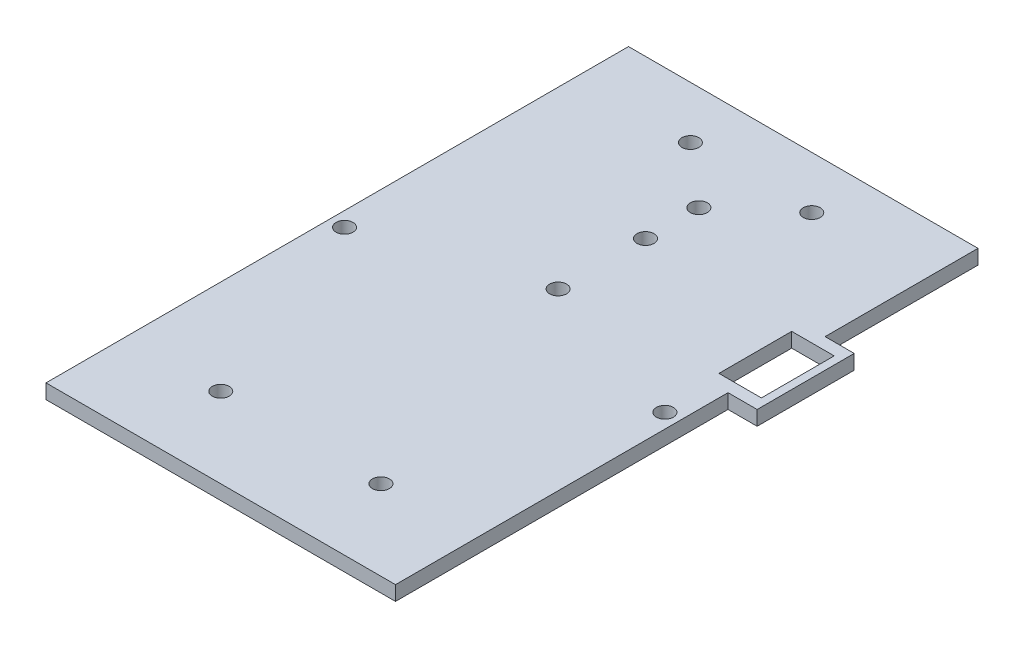
SolidWorks part; units mm, degrees
ref_plane "Front Plane" through (0, 0, 0) normal (0, 0, 1) x (1, 0, 0)
ref_plane "Top Plane" through (0, 0, 0) normal (0, 1, 0) x (1, 0, 0)
ref_plane "Right Plane" through (0, 0, 0) normal (1, 0, 0) x (0, 0, -1)
sketch "Sketch1" plane through (0, 0, 0) normal (0, 1, 0) x (1, 0, 0)
  line L0 (0, 0) -> (0, 50000) construction
  line L1 (36, -60) -> (-36, -60)
  line L2 (36, -60) -> (36, 60)
  line L3 (36, 60) -> (-36, 60)
  line L4 (-36, -60) -> (-36, 60)
  line L5 (36, -60) -> (-36, 60) construction
  line L6 (36, 60) -> (-36, -60) construction
  line L7 (0, 18.5) -> (36, 18.5) construction
  line L8 (0, 9.5) -> (0, -1.5)
  line L9 (0, 0) -> (50000, 0) construction
  line L10 (-20.7309, 49.25) -> (20.7309, 49.25) construction
  line L11 (30, 8.5) -> (42, 8.5)
  line L12 (30, 8.5) -> (30, 28.5)
  line L13 (30, 28.5) -> (42, 28.5)
  line L14 (42, 8.5) -> (42, 28.5)
  line L15 (30, 8.5) -> (42, 28.5) construction
  line L16 (30, 28.5) -> (42, 8.5) construction
  line L17 (40.375, 11) -> (31.625, 11)
  line L18 (40.375, 11) -> (40.375, 26)
  line L19 (40.375, 26) -> (31.625, 26)
  line L20 (31.625, 11) -> (31.625, 26)
  line L21 (40.375, 11) -> (31.625, 26) construction
  line L22 (40.375, 26) -> (31.625, 11) construction
  circle A0 centre (-33, -1.5) radius 1.75
  circle A1 centre (33, -1.5) radius 1.75
  circle A2 centre (-16.5, -43.5) radius 1.75
  circle A3 centre (16.5, -43.5) radius 1.75
  circle A4 centre (0, 27.5) radius 1.75
  circle A5 centre (0, 9.5) radius 1.75
  circle A10 centre (0, 38.5) radius 1.75
  circle A11 centre (0, 38.5) radius 1.75 construction
  circle A12 centre (-12.5, 49.25) radius 1.75
  circle A13 centre (12.5, 49.25) radius 1.75
  point P0 (0, 0)
  point P29 (36, 0)
  point P32 (36, 18.5)
  point P44 (0, 60)
  point P45 (0, 38.5)
  point P46 (0, 49.25)
  point P47 (0, 46.9563)
  point P48 (0, 38.5)
  point P49 (0, 0)
  point P52 (0, 49.25)
  point P53 (0, 0)
  point P54 (0, 0)
  point P55 (0, 0)
  dimension "D3" = 3.5
  dimension "D4" = 3.5
  dimension "D5" = 33
  dimension "D6" = 3.5
  dimension "D7" = 3.5
  dimension "D10" = 3.5
  dimension "D11" = 3.5
  dimension "D15" = 20
  dimension "D16" = 12
  dimension "D17" = 15
  dimension "D19" = 66
  dimension "D12" = 9
  dimension "D20" = 3.5
  dimension "D21" = 3.5
  dimension "D1" = 120
  dimension "D2" = 72
  dimension "D8" = 42
  dimension "D9" = 16.5
  dimension "D13" = 18
  dimension "D14" = 11
  dimension "D18" = 8.75
  dimension "D22" = 25
extrude "Boss-Extrude1" add sketch "Sketch1" along normal blind 3 contours L12 L13 L2 L3 L4 L1 L11 A10 A5 A4 A3 A2 A1 A0 | L19 L18 L17 L2 L11 L14 L13 | L17 L20 L19 L2 L13 L12 L11 region at (-0.4696, 0, 0.3591) region at (33, 0, -8.7088) region at (36.2088, 0, -9.75)
